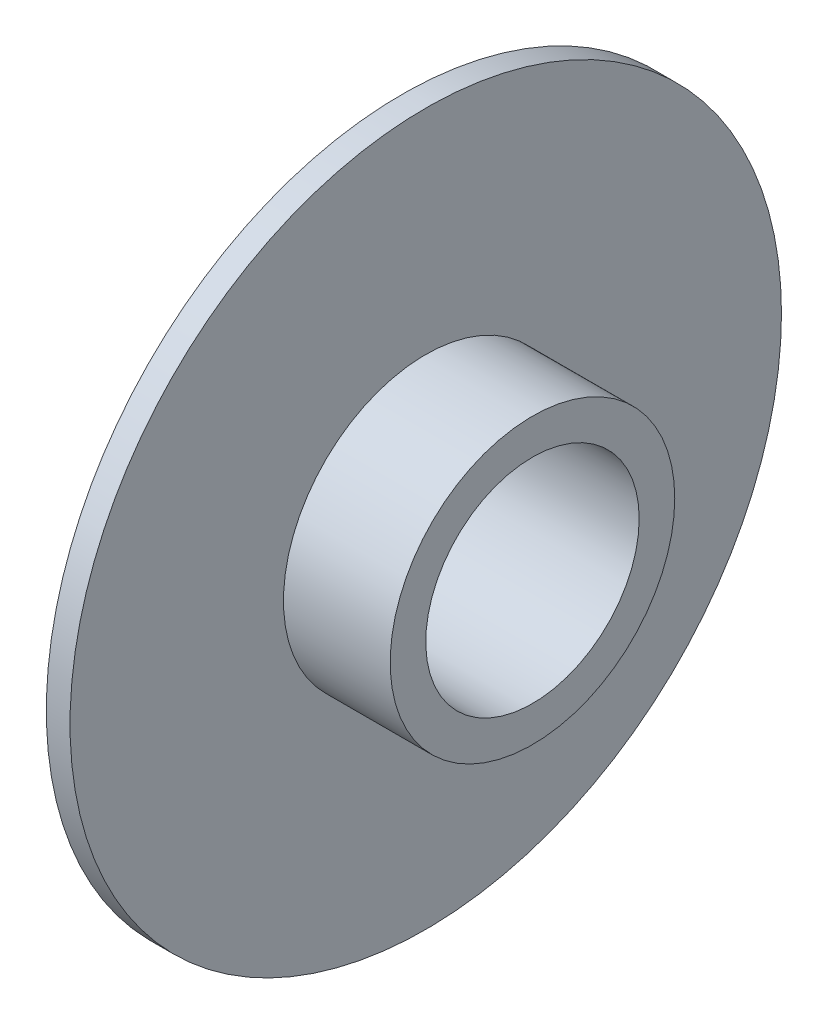
SolidWorks part; units mm, degrees
ref_plane "Front Plane" through (0, 0, 0) normal (0, 0, 1) x (1, 0, 0)
ref_plane "Top Plane" through (0, 0, 0) normal (0, 1, 0) x (1, 0, 0)
ref_plane "Right Plane" through (0, 0, 0) normal (1, 0, 0) x (0, 0, -1)
sketch "Sketch1" plane through (0, 0, 0) normal (1, 0, 0) x (0, 0, -1)
  line L1 (-5, 40) -> (5, 40)
  line L2 (-5, 40) -> (-5, 50)
  line L3 (-5, 50) -> (5, 50)
  line L4 (5, 40) -> (5, 50)
  line L5 (-5, 40) -> (5, 50) construction
  line L6 (-5, 50) -> (5, 40) construction
  circle A0 centre (0, 0) radius 45
  circle A1 centre (0, 0) radius 60
  circle A2 centre (0, 0) radius 150
  point P5 (0, 45)
  dimension "D1" = 90
  dimension "D3" = 120
  dimension "D4" = 300
  dimension "D2" = 10
extrude "Boss-Extrude1" add sketch "Sketch1" along normal mid plane 100 contours A1 A0 L2 L3 L4 region at (0, 0, 58.3029)
extrude "Boss-Extrude2" add sketch "Sketch1<3>" along normal mid plane 10 contours A2 A1 region at (0, 0, 145.7574)
sketch "Sketch1<3>" plane through (0, 0, 0) normal (1, 0, 0) x (0, 0, -1) same geometry as "Sketch1"
sketch "Sketch2" plane through (50, 0, 0) normal (1, 0, 0) x (0, 0, -1)
  line L1 (-5, 50) -> (5.0725, 50)
  line L2 (-5, 50) -> (-5, 44.7214)
  line L4 (5.0725, 50) -> (5.0725, 44.7132)
  arc A0 (5.0725, 44.7132) -> (-5, 44.7214) centre (0, 0) ccw
  arc A1 (-5, 44.7214) -> (5, 44.7214) centre (0, 0) ccw construction
extrude "Boss-Extrude3" add sketch "Sketch2" against normal blind 10
